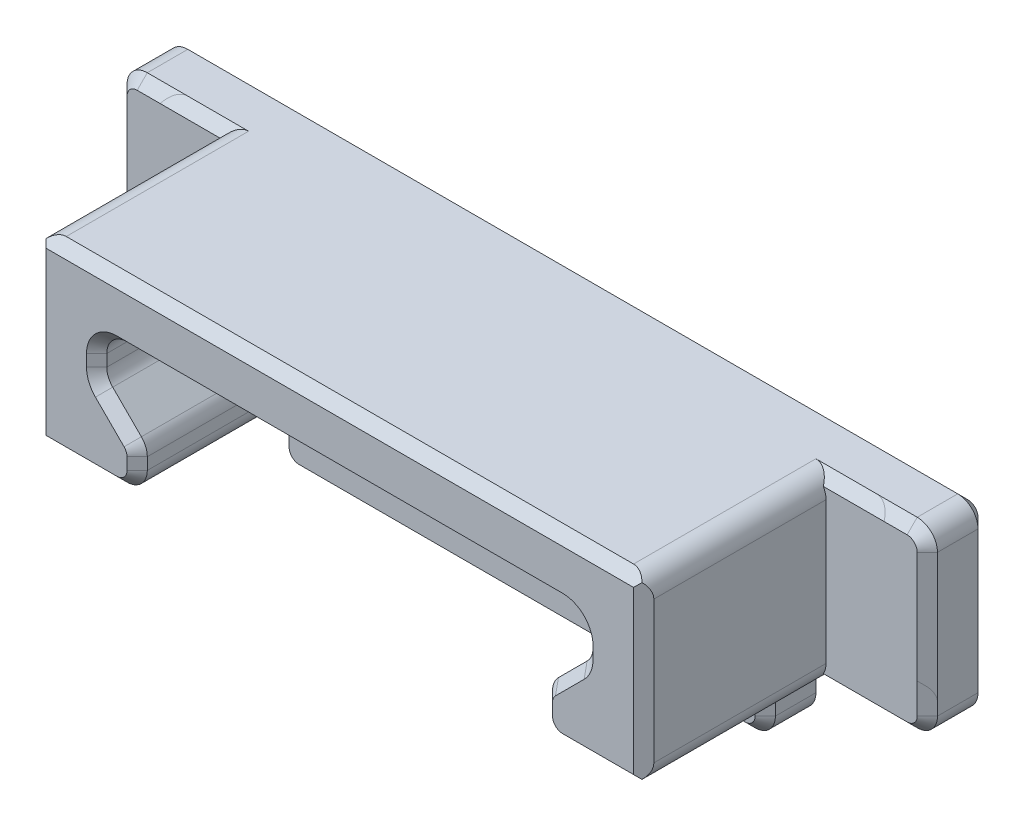
SolidWorks part; units mm, degrees
material "6061 合金"
ref_plane "前视基准面" through (0, 0, 0) normal (0, 0, 1) x (1, 0, 0)
ref_plane "上视基准面" through (0, 0, 0) normal (0, 1, 0) x (1, 0, 0)
ref_plane "右视基准面" through (0, 0, 0) normal (1, 0, 0) x (0, 0, -1)
other "Configuration Table"
sketch "草图1" plane through (0, 0, 0) normal (0, 0, 1) x (1, 0, 0)
  line L0 (0, 66.7358) -> (0, -48.9578) construction
  line L1 (-131.2836, 0) -> (81.2317, 0) construction
  line L42 (-17, 0) -> (17, 0)
  line L43 (18, -4.5858) -> (18, -1)
  line L44 (11, -3) -> (-11, -3)
  line L45 (-12, -4) -> (-12, -4.5858)
  line L46 (-11.7071, -5.2929) -> (-10.2929, -6.7071)
  line L47 (-10, -7.4142) -> (-10, -8)
  line L48 (-11, -9) -> (-19, -9)
  line L49 (-20, -8) -> (-20, -7.4142)
  line L50 (-19.7071, -6.7071) -> (-18.2929, -5.2929)
  line L51 (-18, -4.5858) -> (-18, -1)
  line L52 (19.7071, -6.7071) -> (18.2929, -5.2929)
  line L53 (20, -8) -> (20, -7.4142)
  line L54 (11, -9) -> (19, -9)
  line L55 (10, -7.4142) -> (10, -8)
  line L56 (11.7071, -5.2929) -> (10.2929, -6.7071)
  line L57 (12, -4) -> (12, -4.5858)
  arc A0 (-19, -9) -> (-20, -8) centre (-19, -8) cw
  arc A1 (-10, -8) -> (-11, -9) centre (-11, -8) cw
  arc A2 (18, -1) -> (17, 0) centre (17, -1) ccw
  arc A3 (18, -4.5858) -> (18.2929, -5.2929) centre (19, -4.5858) ccw
  arc A4 (19.7071, -6.7071) -> (20, -7.4142) centre (19, -7.4142) cw
  arc A5 (20, -8) -> (19, -9) centre (19, -8) cw
  arc A6 (11, -9) -> (10, -8) centre (11, -8) cw
  arc A7 (10, -7.4142) -> (10.2929, -6.7071) centre (11, -7.4142) cw
  arc A8 (11.7071, -5.2929) -> (12, -4.5858) centre (11, -4.5858) ccw
  arc A9 (12, -4) -> (11, -3) centre (11, -4) ccw
  arc A10 (-18, -1) -> (-17, 0) centre (-17, -1) cw
  arc A11 (-18.2929, -5.2929) -> (-18, -4.5858) centre (-19, -4.5858) ccw
  arc A12 (-20, -7.4142) -> (-19.7071, -6.7071) centre (-19, -7.4142) cw
  arc A13 (-10.2929, -6.7071) -> (-10, -7.4142) centre (-11, -7.4142) cw
  arc A14 (-12, -4.5858) -> (-11.7071, -5.2929) centre (-11, -4.5858) ccw
  arc A15 (-11, -3) -> (-12, -4) centre (-11, -4) ccw
  point P6 (0, 0)
  point P9 (0, -10)
  point P18 (0, -6)
  point P25 (0, -3)
  dimension "D3" = 1
  dimension "D1" = 3
  dimension "D2" = 45
  dimension "D4" = 9
  dimension "D5" = 10
  dimension "D6" = 36
extrude "凸台-拉伸1" add sketch "草图1" along normal blind 12
sketch "草图2" plane through (0, 0, 0) normal (0, 0, -1) x (-1, 0, 0)
  line L5 (0, -23.2578) -> (0, 33.5795) construction
  line L11 (-19, -9) -> (-13, -9)
  line L12 (-20, -8) -> (-20, -1)
  line L13 (-19, 0) -> (19, 0)
  line L14 (20, -8) -> (20, -1)
  line L15 (-12, -10) -> (-12, -12)
  line L16 (-11, -13) -> (11, -13)
  line L17 (12, -12) -> (12, -10)
  line L18 (13, -9) -> (19, -9)
  arc A8 (11, -13) -> (12, -12) centre (11, -12) ccw
  arc A9 (-12, -12) -> (-11, -13) centre (-11, -12) ccw
  arc A10 (12, -10) -> (13, -9) centre (13, -10) cw
  arc A11 (-12, -10) -> (-13, -9) centre (-13, -10) ccw
  arc A12 (-20, -1) -> (-19, 0) centre (-19, -1) cw
  arc A13 (-19, -9) -> (-20, -8) centre (-19, -8) cw
  arc A14 (19, -9) -> (20, -8) centre (19, -8) ccw
  arc A15 (19, 0) -> (20, -1) centre (19, -1) cw
  dimension "D1" = 40
  dimension "D2" = 9
  dimension "D6" = 1
  dimension "D3" = 4
  dimension "D4" = 24
  dimension "D5" = 8
extrude "凸台-拉伸2" add sketch "草图2" against normal blind 3
sketch "草图7" plane through (0, 0, 0) normal (0, 0, -1) x (-1, 0, 0)
  line L0 (-11, -13) -> (11, -13) construction
  line L6 (3, -13) -> (-3, -13)
  line L7 (4, -12) -> (4, -6)
  line L8 (3, -5) -> (-3, -5)
  line L9 (-4, -12) -> (-4, -6)
  line L10 (4, -13) -> (-4, -5) construction
  line L11 (4, -5) -> (-4, -13) construction
  arc A0 (4, -6) -> (3, -5) centre (3, -6) ccw
  arc A1 (3, -13) -> (4, -12) centre (3, -12) ccw
  arc A2 (-3, -13) -> (-4, -12) centre (-3, -12) cw
  arc A3 (-3, -5) -> (-4, -6) centre (-3, -6) ccw
  point P0 (0, -9)
  dimension "D4" = 1
  dimension "D1" = 8
  dimension "D2" = 8
extrude "凸台-拉伸3" add sketch "草图7" along normal blind 3.5
hole_wizard "M3 螺纹孔1" positions "草图3" profile "草图4" tap size "M3" standard "ISO" end condition through all
sketch "草图3" plane through (0, 0, 3) normal (0, 0, 1) x (1, 0, 0)
  line L1 (17, 0) -> (-17, 0) construction
  point P0 (0, -9)
  dimension "D1" = 9
sketch "草图4" plane through (0, -9, 3) normal (1, 0, 0) x (0, -1, 0)
  line L0 (0, 0) -> (0, 6.5)
  line L1 (0, 6.5) -> (1.25, 6.5)
  line L2 (1.25, 6.5) -> (1.25, 0)
  line L5 (1.25, 0) -> (0, 0)
  line L11 (0, -6.35) -> (0, 107.95) construction
  dimension "通孔螺纹孔钻头直径" = 2.5
  dimension "通孔螺纹孔钻头深度" = 6.5
cosmetic thread "孔螺蚊线3" parameters "D2"=3
chamfer "倒角1" distance 0.5 angle 45 70 edges at (0, -3, 12) (11.7071, -3.2929, 12) (-11.7071, -3.2929, 12) (12, -4.2929, 12) (-12, -4.2929, 12) (11.9239, -4.9685, 12) (-11.9239, -4.9685, 12) (11, -6, 12) (-11, -6, 12) (10.0761, -7.0315, 12) (-10.0761, -7.0315, 12) (10, -7.7071, 12) (-10, -7.7071, 12) (10.2929, -8.7071, 12) (-10.2929, -8.7071, 12) (15, -9, 12) (-15, -9, 12) (19.7071, -8.7071, 12) (-19.7071, -8.7071, 12) (20, -7.7071, 12) (-20, -7.7071, 12) (19.9239, -7.0315, 12) (-19.9239, -7.0315, 12) (19, -6, 12) (-19, -6, 12) (18.0761, -4.9685, 12) (-18.0761, -4.9685, 12) (18, -2.7929, 12) (-18, -2.7929, 12) (17.7071, -0.2929, 12) (-17.7071, -0.2929, 12) (0, 0, 12) (18, 0, 3) (20, -4.2071, 3) (19.7071, -0.2929, 3) (-20, -4.2071, 3) (-18, 0, 3) (-19.7071, -0.2929, 3) (0, -13, -3.5) (-3.7071, -12.7071, -3.5) (3.7071, -12.7071, -3.5) (-4, -9, -3.5) (4, -9, -3.5) (-3.7071, -5.2929, -3.5) (3.7071, -5.2929, -3.5) (0, -5, -3.5) (7, -13, 0) (-7, -13, 0) (11.7071, -12.7071, 0) (-11.7071, -12.7071, 0) (12, -11, 0) (-12, -11, 0) (12.2929, -9.2929, 0) (-12.2929, -9.2929, 0) (16, -9, 0) (-16, -9, 0) (19.7071, -8.7071, 0) (-19.7071, -8.7071, 0) (20, -4.5, 0) (-20, -4.5, 0) (19.7071, -0.2929, 0) (-19.7071, -0.2929, 0) (0, 0, 0) (12.2929, -9.2929, 3) (-12.2929, -9.2929, 3) (12, -11, 3) (-12, -11, 3) (11.7071, -12.7071, 3) (-11.7071, -12.7071, 3) (0, -13, 3)
sketch "草图8" plane through (0, 0, 12) normal (0, 0, 1) x (1, 0, 0)
  line L0 (19, -9) -> (11, -9) construction
  line L1 (15, -9) -> (23.3735, -9)
  line L2 (15, -9) -> (15, 0)
  line L3 (15, 0) -> (23.3735, 0)
  line L4 (23.3735, -9) -> (23.3735, 0)
  line L5 (-17, 0) -> (17, 0) construction
  line L6 (12, -4.5858) -> (12, -4) construction
  line L7 (0, 5.3319) -> (0, -17.4125) construction
  line L8 (-23.3735, -9) -> (-23.3735, 0)
  line L9 (-15, 0) -> (-23.3735, 0)
  line L10 (-15, -9) -> (-15, 0)
  line L11 (-15, -9) -> (-23.3735, -9)
  dimension "D1" = 3
extrude "切除-拉伸1" cut sketch "草图8" against normal up to surface (9 mm away) and the other way through all up to face at (-18.6036, -2.7565, 3)
fillet "圆角1" radius 1 4 edges at (-15, -9, 7.25) (-15, 0, 7.25) (15, 0, 7.25) (15, -9, 7.25)
chamfer "倒角2" distance 0.5 angle 45 8 edges at (-19.7071, -8.7071, 3) (-16.5, -9, 3) (-15, -4.5, 12) (15, -4.5, 12) (-15.5, 0, 3) (15.5, 0, 3) (19.7071, -8.7071, 3) (16.5, -9, 3)
